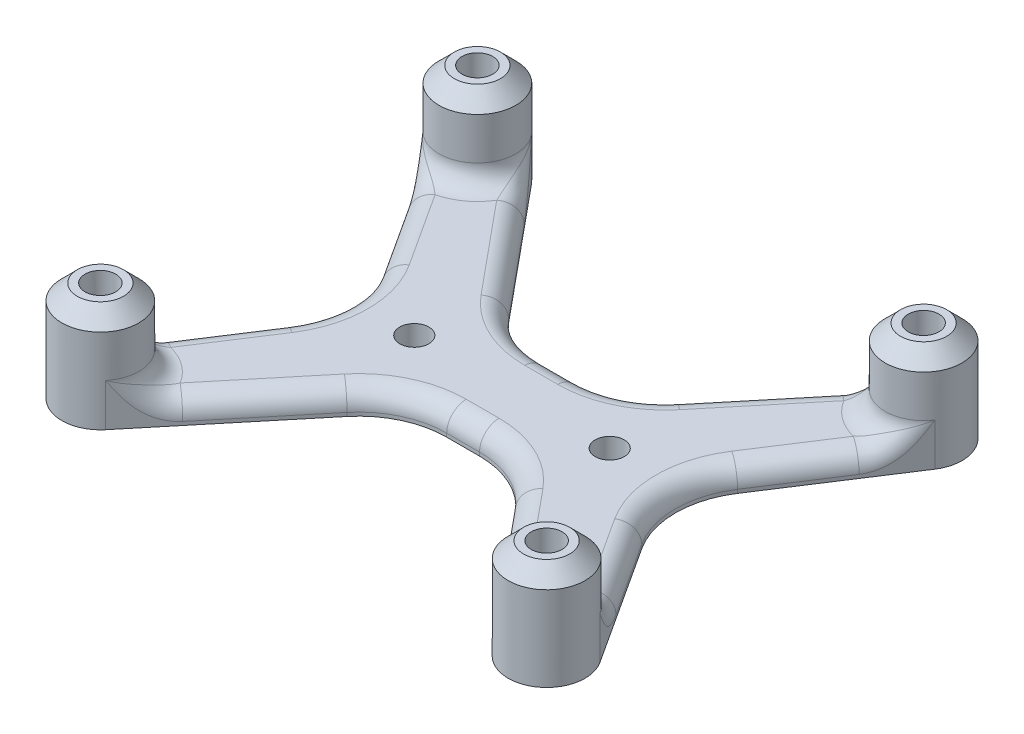
SolidWorks part; units mm, degrees
ref_plane "Front Plane" through (0, 0, 0) normal (0, 0, 1) x (1, 0, 0)
ref_plane "Top Plane" through (0, 0, 0) normal (0, 1, 0) x (1, 0, 0)
ref_plane "Right Plane" through (0, 0, 0) normal (1, 0, 0) x (0, 0, -1)
sketch "Sketch1" plane through (0, 0, 0) normal (0, 1, 0) x (1, 0, 0)
  line L0 (-7.5163, 6.35) -> (7.5163, 6.35)
  line L1 (-29, -24.5) -> (29, -24.5) construction
  line L2 (-29, -24.5) -> (-29, 24.5) construction
  line L3 (-29, 24.5) -> (29, 24.5) construction
  line L4 (29, -24.5) -> (29, 24.5) construction
  line L5 (-29, -24.5) -> (29, 24.5) construction
  line L6 (-29, 24.5) -> (29, -24.5) construction
  line L7 (-19.05, -6.35) -> (19.05, -6.35) construction
  line L8 (-19.05, -6.35) -> (-19.05, 6.35) construction
  line L9 (-19.05, 6.35) -> (19.05, 6.35) construction
  line L10 (19.05, -6.35) -> (19.05, 6.35) construction
  line L11 (-19.05, -6.35) -> (19.05, 6.35) construction
  line L12 (-19.05, 6.35) -> (19.05, -6.35) construction
  line L13 (7.5163, 6.35) -> (25.1456, 27.6849)
  line L14 (19.05, 0) -> (33.1932, 21.7766)
  line L15 (19.05, 0) -> (33.1932, -21.7766)
  line L16 (25.1456, -27.6849) -> (7.5163, -6.35)
  line L17 (7.5163, -6.35) -> (-7.5163, -6.35)
  line L18 (-7.5163, -6.35) -> (-25.1456, -27.6849)
  line L19 (-19.05, 0) -> (-33.1932, -21.7766)
  line L20 (-19.05, 0) -> (-33.1932, 21.7766)
  line L21 (-25.1456, 27.6849) -> (-7.5163, 6.35)
  circle A0 centre (-29, -24.5) radius 5
  circle A1 centre (29, -24.5) radius 5
  circle A2 centre (29, 24.5) radius 5
  circle A3 centre (-29, 24.5) radius 5
  point P0 (0, 0)
  point P6 (0, 0)
  dimension "D5" = 10
  dimension "D6" = 10
  dimension "D7" = 10
  dimension "D8" = 10
  dimension "D1" = 12.7
  dimension "D2" = 38.1
  dimension "D3" = 58
  dimension "D4" = 49
extrude "Boss-Extrude1" add sketch "Sketch1" along normal blind 3 contours A0 | A3 L20 L19 A0 L18 L17 L16 A1 L15 L14 A2 L13 L0 L21 | A3 | A2 | A1 region at (0, 0, 0) region at (-29, 0, -24.5) region at (29, 0, -24.5) region at (-29, 0, 24.5) region at (29, 0, 24.5)
sketch "Sketch2" plane through (0, 3, 0) normal (0, 1, 0) x (1, 0, 0)
  circle A0 centre (-29, -24.5) radius 5
  circle A1 centre (29, -24.5) radius 5
  circle A2 centre (29, 24.5) radius 5
  circle A3 centre (-29, 24.5) radius 5
extrude "Boss-Extrude2" add sketch "Sketch2" along normal blind 10
sketch "Sketch3" plane through (0, 13, 0) normal (0, 1, 0) x (1, 0, 0)
  circle A0 centre (-29, -24.5) radius 2
  circle A1 centre (-29, 24.5) radius 2
  circle A2 centre (29, 24.5) radius 2
  circle A3 centre (29, -24.5) radius 2
  dimension "D1" = 4
  dimension "D2" = 4
  dimension "D3" = 4
  dimension "D4" = 4
extrude "Cut-Extrude1" cut sketch "Sketch3" against normal blind 4.8
fillet "Fillet2" radius 11.43 4 edges at (7.5163, 1.5, -6.35) (-7.5163, 1.5, -6.35) (7.5163, 1.5, 6.35) (-7.5163, 1.5, 6.35)
fillet "Fillet3" radius 11.43 2 edges at (-19.05, 1.5, 0) (19.05, 1.5, 0)
fillet "Fillet4" radius 2.54 4 edges at (-26.041, 3, 20.4696) (26.041, 3, 20.4696) (26.041, 3, -20.4696) (-26.041, 3, -20.4696)
fillet "Fillet5" radius 2.54 24 edges at (31.0686, 3.3005, 18.5052) (26.6063, 3, 11.6346) (31.0686, 3.3005, -18.5052) (26.6063, 3, -11.6346) (-22.6609, 3.3005, 24.6779) (-16.2478, 3, 16.9168) (-7.0034, 3, 7.4392) (0, 3, 6.35) (22.6609, 3.3005, 24.6779) (16.2478, 3, 16.9168) (-31.0686, 3.3005, -18.5052) (-26.6063, 3, -11.6346) (-31.0686, 3.3005, 18.5052) (-26.6063, 3, 11.6346) (-22.6609, 3.3005, -24.6779) (-16.2478, 3, -16.9168) (-7.0034, 3, -7.4392) (0, 3, -6.35) (7.0034, 3, -7.4392) (22.6609, 3.3005, -24.6779) (21.2491, 3, 0) (7.0034, 3, 7.4392) (-21.2491, 3, 0) (16.2478, 3, -16.9168)
sketch "Sketch4" plane through (0, 3, 0) normal (0, 1, 0) x (1, 0, 0)
  circle A0 centre (-12.7, 0) radius 1.8923
  circle A1 centre (12.7, 0) radius 1.8923
  dimension "D1" = 3.7846
  dimension "D3" = 3.7846
  dimension "D2" = 12.7
  dimension "D4" = 12.7
extrude "Cut-Extrude2" cut sketch "Sketch4" against normal through all
chamfer "Chamfer1" distance 2 angle 45 4 edges at (-29, 13, 29.5) (-29, 13, -19.5) (29, 13, -19.5) (29, 13, 29.5)
sketch "Sketch5" plane through (0, 8.2, 0) normal (0, 1, 0) x (1, 0, 0)
  circle A0 centre (-29, -24.5) radius 1.6
  dimension "D1" = 3.2
extrude "Cut-Extrude3" cut sketch "Sketch5" against normal through all
mirror "Mirror1" about plane through (0, 0, 0) normal (1, 0, 0) of "Cut-Extrude3" second plane through (0, 0, 0) second plane normal (0, 0, 1)
